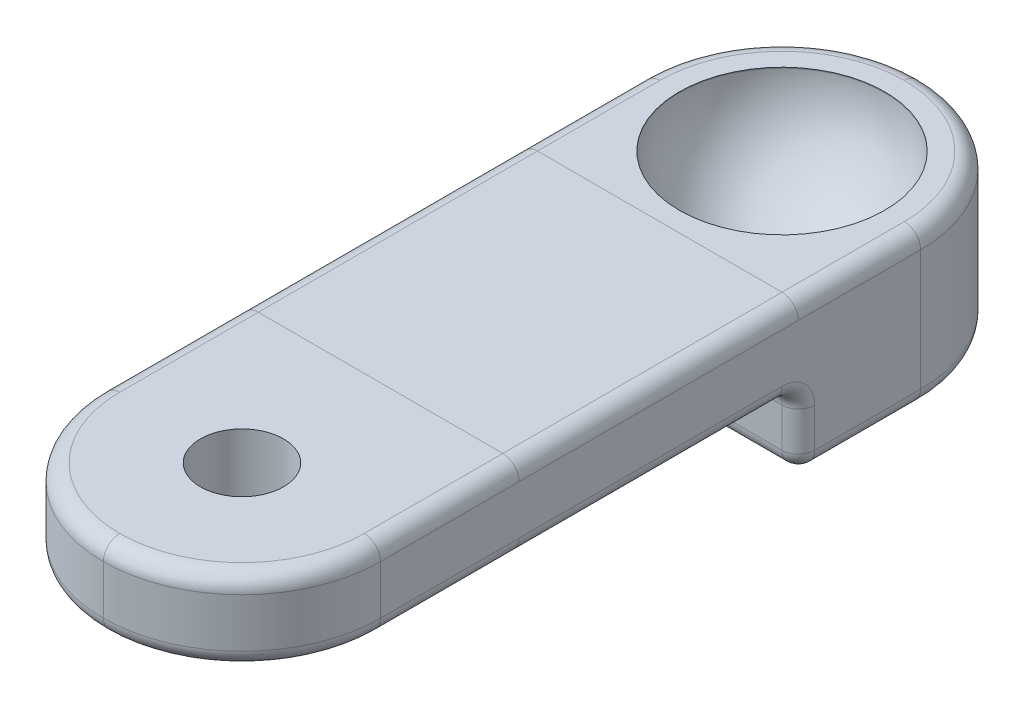
SolidWorks part; units mm, degrees
ref_plane "Front Plane" through (0, 0, 0) normal (0, 0, 1) x (1, 0, 0)
ref_plane "Top Plane" through (0, 0, 0) normal (0, 1, 0) x (1, 0, 0)
ref_plane "Right Plane" through (0, 0, 0) normal (1, 0, 0) x (0, 0, -1)
sketch "ProfileSketch1" plane through (0, 0, 0) normal (1, 0, 0) x (0, 0, -1)
  line L0 (0, 0) -> (34, 0)
  line L1 (34, 0) -> (68.2531, 0)
  line L2 (68.2531, 0) -> (100.2531, 0)
  line L3 (17, 0) -> (17, 2.8642) construction
  line L4 (84.2531, 0) -> (84.2531, 2.8642) construction
  dimension "D1" = 34
  dimension "D2" = 0
  dimension "D4" = 32
  dimension "D3" = 67.2531
extrude "ProfileExtrude-Thin1" add sketch "ProfileSketch1" along normal blind 34 thin thin type one direction wall 10
sketch "DomePadExtensionSketch1" plane through (0, -10, 0) normal (0, -1, 0) x (1, 0, 0)
  line L1 (0, -68.2531) -> (34, -68.2531)
  line L2 (0, -68.2531) -> (0, -100.2531)
  line L3 (0, -100.2531) -> (34, -100.2531)
  line L4 (34, -68.2531) -> (34, -100.2531)
extrude "DomePadExtensionBoss-Extrude1" add sketch "DomePadExtensionSketch1" along normal blind 8.8
fillet "Fillet1" radius 17 1 edges at (34, -5, 0)
fillet "Fillet2" radius 17 1 edges at (0, -5, 0)
sketch "FlangeNutHoleSketch4" plane through (0, 0, 0) normal (0, 1, 0) x (1, 0, 0)
  line L0 (0, 17) -> (0, 34) construction
  line L1 (34, 34) -> (0, 34) construction
  circle A0 centre (17, 17) radius 5.1
  dimension "D1" = 17
  dimension "D3" = 10.2
  dimension "D2" = 17
extrude "FlangeNutHoleCut-Extrude5" cut sketch "FlangeNutHoleSketch4" against normal through all
sketch "DomeIndentSketch6" plane through (0, 0, 0) normal (0, 1, 0) x (1, 0, 0)
  line L4 (0, 68.2531) -> (0, 100.2531) construction
  line L5 (34, 100.2531) -> (0, 100.2531) construction
  circle A0 centre (17, 83.2531) radius 12.6
  dimension "D2" = 17
  dimension "D1" = 25.2
  dimension "D3" = 17
extrude "DomeIndentCut-Extrude8" cut sketch "DomeIndentSketch6" against normal blind 0.1
dome "Dome2" faces to dome 1 distance 12.5 reverse direction yes elliptical dome no face at (17, -0.1, -70.6531) parameters "D1"=12.5
fillet "Fillet3" radius 17 1 edges at (34, -9.4, -100.2531)
fillet "Fillet4" radius 17 1 edges at (0, -9.4, -100.2531)
sketch "FlangeNutHolesSketch2" plane through (0, -10, 0) normal (0, -1, 0) x (1, 0, 0)
  line L0 (32, -31.2943) -> (32, -17) construction
  line L1 (34, -34) -> (0, -34) construction
  circle A0 centre (11.3431, -11.3431) radius 2
  circle A1 centre (22.6569, -11.3431) radius 2
  circle A2 centre (22.6569, -22.6569) radius 2
  circle A3 centre (11.3431, -22.6569) radius 2
  point P16 (17, -17)
  dimension "D2" = 4
  dimension "D1" = 8
  dimension "D4" = 8
  dimension "D3" = 4
fillet "BottomBoundaryFillet5" radius 2 14 edges at (0, -10, -51.1266) (34, -10, -51.1266) (34, -10, -25.5) (29.0208, -10, -4.9792) (4.9792, -10, -4.9792) (0, -10, -25.5) (34, -18.8, -75.7531) (29.0208, -18.8, -95.2739) (4.9792, -18.8, -95.2739) (34, -14.4, -68.2531) (17, -18.8, -68.2531) (0, -14.4, -68.2531) (17, -10, -68.2531) (0, -18.8, -75.7531)
extrude "FlangeNutHolesCut-Extrude1" cut sketch "FlangeNutHolesSketch2" against normal blind 4
fillet "Fillet6" radius 2 10 edges at (34, 0, -51.1266) (34, 0, -25.5) (29.0208, 0, -4.9792) (4.9792, 0, -4.9792) (0, 0, -25.5) (0, 0, -51.1266) (0, 0, -75.7531) (4.9792, 0, -95.2739) (34, 0, -75.7531) (29.0208, 0, -95.2739)
equation "\"D1@ProfileSketch1\"=\"BedSupportLeadScrewPadSize\""
equation "\"StandardWallThickness\"= 3mm"
equation "\"BedToBuildPlateStandoffPadSize\"= 10mm"
equation "\"BuildPlateStandoffHolesDistanceFromLeftOrRight\"= 7mm"
equation "\"BuildPlateStandoffHolesDistanceFromFrontOrBack\"= 41mm"
equation "\"DistanceFromBuildPlateSideToStepperHole\"= ( \"DistanceBetweenLeftToRightStepperHoles\" - \"BuildPlateWidth\" ) / 2'Equals 55.825"
equation "\"DistanceBetweenLeftToRightStepperHoles\"= \"FrontBackRailLength\" - \"StepperMountingHoleOffsetFromLeftOrRightSide\" * 2 - \"StepperMountingHoleDistance\"'Equals 461.65"
equation "\"FrontBackRailLength\"= 510mm"
equation "\"StepperMountingHoleOffsetFromLeftOrRightSide\"= \"StepperMountingHoleOffsetFromItsSide\" + \"RailThickness\""
equation "\"StepperMountingHoleDistance\"= 31mm'Spec"
equation "\"StepperMountingHoleOffsetFromItsSide\"= 5.5mm'Spec"
equation "\"RailThickness\"= .125in'Spec"
equation "\"LeadScrewNutPadSize\"= \"LeadScrewNutMountingHoleFlangeDiameter\" + 2mm'Equals 24"
equation "\"LeadScrewNutInnerShaftFlangeDiameter\"= 10.2mm'Spec"
equation "\"LeadScrewNutMountHoleDiameter\"= \"M3HeatInsertHoleDiameter\""
equation "\"LeadScrewNutMountingHoleFlangeDiameter\"= 22mm'Spec"
equation "\"LeadScrewNutMountingHoleDistance\"= 16mm'Spec"
equation "\"M3HeatInsertHoleDiameter\"= 4mm'Spec"
equation "\"D1@Fillet1\"=\"BedSupportLeadScrewPadSize\"/2"
equation "\"D1@Fillet2\"=\"BedSupportLeadScrewPadSize\"/2"
equation "\"D1@FlangeNutHoleSketch4\"=\"BedSupportLeadScrewPadSize\"  / 2"
equation "\"D2@FlangeNutHoleSketch4\"=\"BedSupportLeadScrewPadSize\" / 2"
equation "\"D3@FlangeNutHoleSketch4\" = \"LeadScrewNutInnerShaftFlangeDiameter\""
equation "\"D2@DomeIndentSketch6\" = \"BedSupportLeadScrewPadSize\" / 2"
equation "\"D3@DomeIndentSketch6\" = \"BedSupportLeadScrewPadSize\" / 2"
equation "\"BedSpringHoleSize\"= 3mm"
equation "\"BuildPlateWidth\"= 350mm'Spec"
equation "\"BuildPlateLength\" = 352mm'Spec"
equation "\"BuildPlateBoreDiameter\"= 5mm'Spec"
equation "\"BuildPlateBoreDepth\"= 3mm'Spec"
equation "\"BuildPlateDepth\"= 8mm'Spec"
equation "\"BuildPlateFlankingHoles\"= 38mm"
equation "\"BuildPlateStandoffHolesDistanceFromFront\"= 7mm"
equation "\"BedSupportLeadScrewPadSize\"= \"LeadScrewNutPadSize\" + 10mm"
equation "\"D1@ProfileExtrude-Thin1\"=\"BedSupportLeadScrewPadSize\""
equation "\"BuildPlateBallDiameter\"= 12mm"
equation "\"BedSupportBuildPlatePadSize\"= \"BuildPlateBallDiameter\" + 20mm"
equation "\"D4@ProfileSketch1\"=\"BedSupportBuildPlatePadSize\""
equation "\"D3@ProfileSketch1\"=\"HypotonusOfStepperAndBuildPlateHoles\""
equation "\"D1@Fillet3\"=\"BedSupportLeadScrewPadSize\"/2"
equation "\"D1@Fillet4\"=\"BedSupportLeadScrewPadSize\"/2"
equation "\"HypotonusOfStepperAndBuildPlateHoles\"= sqr ( ( \"DistanceFromBuildPlateSideToStepperHole\" + \"BuildPlateStandoffHolesDistanceFromLeftOrRight\" ) ^ 2 + ( \"BuildPlateStandoffHolesDistanceFromFrontOrBack\" - \"BedSupportLeadScrewPadSize\" / 2 ) ^ 2 )"
equation "\"D1@FlangeNutHolesCut-Extrude1\" = \"M3HeatInsertHoleDiameter\""
equation "\"D1@FlangeNutHolesSketch2\"=\"LeadScrewNutMountingHoleDistance\"/2"
equation "\"D2@FlangeNutHolesSketch2\"=\"M3HeatInsertHoleDiameter\""
equation "\"D4@FlangeNutHolesSketch2\"=\"LeadScrewNutMountingHoleDistance\"/2"
equation "\"BallNutDiameter\"= \"BallJointDiameter\" + .2mm'Added .2mm for filament expansion"
equation "\"D1@DomeIndentSketch6\"=\"BallNutDiameter\""
equation "\"D1@DomePadExtensionBoss-Extrude1\" = \"BedSupportBuildPlatePadSize\" - \"BallNutDiameter\" + 2mm"
equation "\"BallJointDiameter\"= 25mm"
